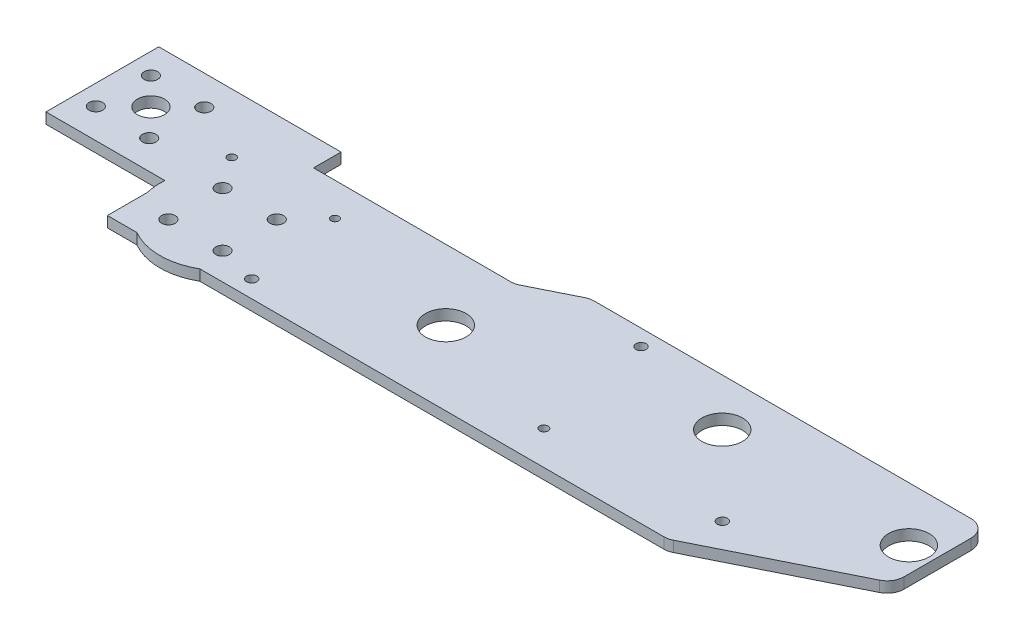
SolidWorks part; units mm, degrees
ref_plane "Front" through (0, 0, 0) normal (0, 0, 1) x (1, 0, 0)
ref_plane "Top" through (0, 0, 0) normal (0, 1, 0) x (1, 0, 0)
ref_plane "Right" through (0, 0, 0) normal (1, 0, 0) x (0, 0, -1)
sketch "Sketch1" plane through (0, 0, 0) normal (0, 1, 0) x (1, 0, 0)
  line L1 (0, 0) -> (210, 0)
  line L2 (0, 0) -> (0, -50)
  line L3 (0, -50) -> (210, -50)
  line L4 (210, 0) -> (210, -50)
  circle A7 centre (3.4895, -16.7877) radius 1.2117
  circle A8 centre (34.3726, -17.194) radius 1.1656
  circle A9 centre (37.5207, -44.9212) radius 1.5
  circle A10 centre (118.879, -40.0177) radius 1.25
  circle A11 centre (112.3021, -4.7393) radius 1.5
  circle A12 centre (168.9752, -37.4032) radius 1.5173
  dimension "D1" = 210
  dimension "D2" = 50
extrude "Boss-Extrude1" add sketch "Sketch1" along normal blind 3.175
sketch "Sketch2" plane through (0, 3.175, 0) normal (0, 1, 0) x (1, 0, 0)
  line L0 (210, 0) -> (0, 0) construction
  line L1 (0, 0) -> (0, -50) construction
  circle A0 centre (10, -26) radius 2
  circle A1 centre (10, -42) radius 2
  circle A2 centre (26, -26) radius 2
  circle A3 centre (26, -42) radius 2
  dimension "D1" = 16
  dimension "D2" = 16
  dimension "D3" = 16
  dimension "D4" = 26
  dimension "D5" = 10
  dimension "D6" = 10
  dimension "D7" = 26
  dimension "D8" = 16
extrude "Cut-Extrude1" cut sketch "Sketch2" against normal blind 10
sketch "Sketch3" plane through (0, 3.175, 0) normal (0, 1, 0) x (1, 0, 0)
  line L0 (210, 0) -> (0, 0) construction
  line L1 (210, 0) -> (0, 0) construction
  circle A0 centre (78.0103, -28.1) radius 6
  circle A1 centre (145.5313, -14) radius 6
  circle A2 centre (18, -34) radius 0.587
  circle A3 centre (26, -26) radius 2 construction
  circle A4 centre (202.6463, -16) radius 6
  dimension "D1" = 28.1
  dimension "D3" = 16
  dimension "D4" = 14
  dimension "D7" = 125.222
  dimension "D2" = 60.2996
  dimension "D5" = 8
  dimension "D6" = 8
  dimension "D8" = 57.15
extrude "Cut-Extrude2" cut sketch "Sketch3" against normal blind 57.15
sketch "Sketch4" [suppressed] plane through (0, 3.175, 0) normal (0, 1, 0) x (1, 0, 0)
  line L0 (3.4895, -16.7877) -> (18, -34)
  line L1 (3.4895, -20.6627) -> (5.9498, -23.5811)
  line L2 (18, -34) -> (34.3726, -17.194)
  line L3 (34.3726, -17.194) -> (75.8499, -28.1)
  line L4 (75.8499, -28.1) -> (37.5207, -44.9212)
  line L5 (7.3432, -17.194) -> (9.8664, -20.303)
  circle A0 centre (18, -34) radius 15.9299
  circle A1 centre (3.4895, -16.7877) radius 3.8751
  circle A2 centre (34.3726, -17.194) radius 3.7227
  circle A3 centre (37.5207, -44.9212) radius 3.8676
  circle A4 centre (75.8499, -28.1) radius 12.797
  circle A5 centre (112.3021, -4.7393) radius 5.1588
  circle A6 centre (118.879, -40.0177) radius 4.9035
  circle A7 centre (140.772, -16) radius 12.6375
  circle A8 centre (168.9752, -37.4032) radius 4.2066
  circle A9 centre (197.922, -16) radius 12.8
sketch "Sketch5" [suppressed] plane through (0, 3.175, 0) normal (0, 1, 0) x (1, 0, 0)
  line L0 (210, 0) -> (0, 0) construction
  line L2 (-0.6266, -16.7877) -> (37.5207, -16.7877)
  line L3 (-0.6266, -16.7877) -> (-0.6266, -44.9212)
  line L4 (-0.6266, -44.9212) -> (37.5207, -44.9212)
  line L5 (37.5207, -16.7877) -> (37.5207, -44.9212)
  line L6 (75.8499, -15.182) -> (37.5207, -15.182)
  line L7 (75.8499, -15.182) -> (75.8499, -44.9212)
  line L8 (75.8499, -44.9212) -> (37.5207, -44.9212)
  line L9 (37.5207, -15.182) -> (37.5207, -44.9212)
  line L10 (112.3021, -4.7393) -> (75.8499, -4.7393)
  line L11 (112.3021, -4.7393) -> (112.3021, -44.9212)
  line L12 (112.3021, -44.9212) -> (75.8499, -44.9212)
  line L13 (75.8499, -4.7393) -> (75.8499, -44.9212)
  line L14 (112.3021, -4.7393) -> (102.3945, -4.7393)
  line L16 (112.3021, -4.7393) -> (112.3021, 0)
  line L17 (112.3021, 0) -> (102.3945, 0)
  line L18 (102.3945, -4.7393) -> (102.3945, 0)
  line L19 (210, -50) -> (210, 0) construction
  line L20 (112.3021, -4.7393) -> (123.1553, -4.7393)
  line L21 (112.3021, -4.7393) -> (112.3021, 0)
  line L22 (112.3021, 0) -> (123.1553, 0)
  line L23 (123.1553, -4.7393) -> (123.1553, 0)
  line L24 (112.3021, -4.7393) -> (140.772, -4.7393)
  line L25 (112.3021, -4.7393) -> (112.3021, -40.0177)
  line L26 (112.3021, -40.0177) -> (140.772, -40.0177)
  line L27 (140.772, -4.7393) -> (140.772, -40.0177)
  line L28 (140.772, -16) -> (168.9752, -16)
  line L29 (140.772, -16) -> (140.772, -40.0177)
  line L30 (140.772, -40.0177) -> (168.9752, -40.0177)
  line L31 (168.9752, -16) -> (168.9752, -40.0177)
  line L32 (168.9752, -4.7393) -> (210, -4.7393)
  line L33 (168.9752, -4.7393) -> (168.9752, -40.0177)
  line L34 (168.9752, -40.0177) -> (210, -40.0177)
  line L35 (210, -4.7393) -> (210, -40.0177)
  line L36 (0, -50) -> (210, -50) construction
  line L37 (160.7629, -40.0177) -> (177.2091, -40.0177)
  line L38 (160.7629, -40.0177) -> (160.7629, -44.9212)
  line L39 (160.7629, -44.9212) -> (177.2091, -44.9212)
  line L40 (177.2091, -40.0177) -> (177.2091, -44.9212)
  line L41 (112.3021, -40.0177) -> (126.3591, -40.0177)
  line L42 (112.3021, -40.0177) -> (112.3021, -47.7828)
  line L43 (112.3021, -47.7828) -> (126.3591, -47.7828)
  line L44 (126.3591, -40.0177) -> (126.3591, -47.7828)
  line L45 (30.5963, -44.9212) -> (44.6115, -44.9212)
  line L46 (30.5963, -44.9212) -> (30.5963, -50)
  line L47 (30.5963, -50) -> (44.6115, -50)
  line L48 (44.6115, -44.9212) -> (44.6115, -50)
  line L50 (-0.6266, -44.9212) -> (30.5963, -44.9212)
  line L51 (-0.6266, -44.9212) -> (-0.6266, -50)
  line L52 (-0.6266, -50) -> (30.5963, -50)
  line L53 (30.5963, -44.9212) -> (30.5963, -50)
  circle A0 centre (3.4895, -16.7877) radius 4.1161
  circle A1 centre (34.3726, -17.194) radius 3.8132
  circle A2 centre (75.8499, -28.1) radius 12.918
  circle A3 centre (112.3021, -4.7393) radius 5.2663
  circle A4 centre (140.772, -16) radius 13.0245
  circle A5 centre (197.922, -16) radius 12.3805
  circle A6 centre (168.9752, -37.4032) radius 4.7643
  circle A7 centre (118.879, -40.0177) radius 5.279
  circle A8 centre (37.5207, -44.9212) radius 4.2049
  line M12 (0, 0) -> (0, -50)
  line M13 (0, -50) -> (210, -50)
  line M14 (210, -50) -> (210, 0)
  line M15 (210, 0) -> (0, 0)
extrude "Cut-Extrude5" [suppressed] cut sketch "Sketch5" against normal blind 11.52 contours A5 L32 L23 L24 A4 L28 L33 M14 M15 | A1 L6 L13 L10 L18 A0 L2 M15 M12 | L8 L48 L34 L40 L39 L38 L30 L26 L44 L43 L42 L12 M13 M14
fillet "Fillet1" [suppressed] radius 5
sketch "Sketch10" plane through (0, 3.175, 0) normal (0, 1, 0) x (1, 0, 0)
  line L0 (210, -27.8594) -> (165.5029, -50)
  line L1 (210, -50) -> (210, 0) construction
  line L2 (0, -50) -> (210, -50) construction
  line L3 (165.5029, -50) -> (210, -50)
  line L4 (210, -50) -> (210, -27.8594)
  line L5 (92.5326, 0) -> (77.6548, -7.4028)
  line L6 (210, 0) -> (0, 0) construction
  line L7 (77.6548, -7.4028) -> (0, -7.4028)
  line L8 (0, 0) -> (0, -50) construction
  line L9 (0, -7.4028) -> (0, 0)
  line L10 (0, 0) -> (92.5326, 0)
extrude "Cut-Extrude7" cut sketch "Sketch10" against normal blind 10
fillet "Fillet3" radius 5 5 edges at (77.6548, 1.5875, 7.4028) (92.5326, 1.5875, 0) (210, 1.5875, 0) (210, 1.5875, 27.8594) (165.5029, 1.5875, 50)
sketch "Sketch11" plane through (0, 3.175, 0) normal (0, 1, 0) x (1, 0, 0)
  circle A0 centre (18, -34) radius 18.5
  circle A1 centre (10, -26) radius 2
  circle A2 centre (10, -42) radius 2
  circle A3 centre (26, -26) radius 2
  circle A4 centre (26, -42) radius 2
extrude "Boss-Extrude4" add sketch "Sketch11" against normal blind 3.175
sketch "Sketch16" plane through (0, 0, 7.4028) normal (0, 0, -1) x (-1, 0, 0)
  line L0 (0, 3.175) -> (-76.4796, 3.175) construction
  line L1 (0, 0) -> (-18.2576, 0)
  line L2 (0, 0) -> (0, 3.175)
  line L3 (0, 3.175) -> (-18.2576, 3.175)
  line L4 (-18.2576, 0) -> (-18.2576, 3.175)
extrude "Boss-Extrude7" add sketch "Sketch16" along normal blind 8.128
sketch "Sketch17" plane through (0, 0, 0) normal (-1, 0, 0) x (0, 0, 1)
  line L0 (-0.7252, 3.175) -> (29.728, 3.175) construction
  line L1 (-0.7252, 0) -> (32.5748, 0)
  line L2 (-0.7252, 0) -> (-0.7252, 3.175)
  line L3 (-0.7252, 3.175) -> (32.5748, 3.175)
  line L4 (32.5748, 0) -> (32.5748, 3.175)
  dimension "D1" = 33.3
extrude "Boss-Extrude8" add sketch "Sketch17" along normal blind 35.56
sketch "Sketch18" plane through (0, 3.175, 0) normal (0, 1, 0) x (1, 0, 0)
  line L0 (-35.56, 0.7252) -> (18.2576, 0.7252) construction
  circle A0 centre (-21.4859, -15.9248) radius 11.315
  circle A1 centre (-29.612, -23.7985) radius 2
  circle A2 centre (-29.3597, -7.7987) radius 2
  circle A3 centre (-13.3598, -8.0511) radius 2
  circle A4 centre (-13.6122, -24.0509) radius 2
  circle A5 centre (-21.4859, -15.9248) radius 4
  point P15 (-21.4859, -15.9248)
  dimension "D1" = 22.63
  dimension "D3" = 4
  dimension "D2" = 16.65
extrude "Cut-Extrude8" cut sketch "Sketch18" against normal blind 9 contours A2 | A1 | A4 | A3
sketch "Sketch19" plane through (0, 3.175, 0) normal (0, 1, 0) x (1, 0, 0)
  circle A0 centre (-21.3597, -15.7987) radius 4
  circle A1 centre (-29.3597, -7.7987) radius 2 construction
  dimension "D1" = 8
  dimension "D2" = 8
extrude "Cut-Extrude9" cut sketch "Sketch19" against normal blind 40
